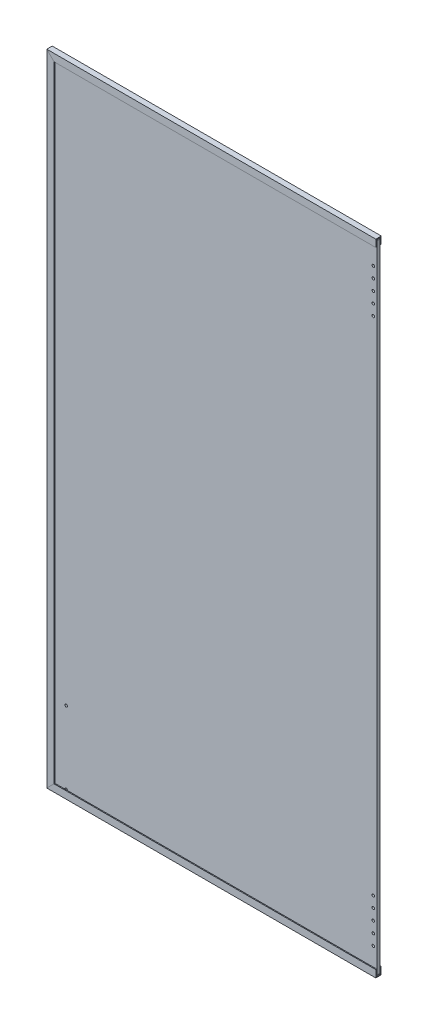
SolidWorks part; units mm, degrees
material "PC High Viscosity"
ref_plane "Front Plane" through (0, 0, 0) normal (0, 0, 1) x (1, 0, 0)
ref_plane "Top Plane" through (0, 0, 0) normal (0, 1, 0) x (1, 0, 0)
ref_plane "Right Plane" through (0, 0, 0) normal (1, 0, 0) x (0, 0, -1)
sketch "Shelf opening" plane through (0, 0, 0) normal (0, 0, 1) x (1, 0, 0)
  line L1 (0, 0) -> (577.85, 0)
  line L2 (0, 0) -> (0, 1092.2)
  line L3 (0, 1092.2) -> (577.85, 1092.2)
  line L4 (577.85, 0) -> (577.85, 1092.2)
  dimension "D1" = 577.85
  dimension "D2" = 1092.2
sketch "Sketch2" plane through (0, 0, 0) normal (0, 0, 1) x (1, 0, 0)
  line L0 (577.85, 0) -> (577.85, 1092.2) construction
  line L1 (3.175, 1104.9) -> (577.85, 1104.9)
  line L2 (3.175, 1104.9) -> (3.175, -12.7)
  line L3 (3.175, -12.7) -> (577.85, -12.7)
  line L4 (577.85, 1104.9) -> (577.85, -12.7)
  line L5 (0, 1092.2) -> (577.85, 1092.2) construction
  line L6 (0, 0) -> (0, 1092.2) construction
  line L7 (0, 0) -> (577.85, 0) construction
  dimension "D1" = 12.7
  dimension "D2" = 3.175
  dimension "D3" = 12.7
extrude "Frame outer dimensions" add sketch "Sketch2" along normal mid plane 9.525
sketch "Sketch3" plane through (0, 0, 4.7625) normal (0, 0, 1) x (1, 0, 0)
  line L0 (577.85, -12.7) -> (577.85, 1104.9) construction
  line L1 (577.85, 1092.2) -> (15.875, 1092.2)
  line L2 (577.85, 1092.2) -> (577.85, 0)
  line L3 (577.85, 0) -> (15.875, 0)
  line L4 (15.875, 1092.2) -> (15.875, 0)
  line L5 (577.85, 1104.9) -> (3.175, 1104.9) construction
  line L6 (3.175, 1104.9) -> (3.175, -12.7) construction
  line L7 (3.175, -12.7) -> (577.85, -12.7) construction
  dimension "D1" = 12.7
  dimension "D2" = 12.7
  dimension "D3" = 12.7
extrude "Frame inner dimensions" cut sketch "Sketch3" against normal through all
sketch "Sketch4" plane through (0, 0, 0) normal (0, 0, 1) x (1, 0, 0)
  line L0 (577.85, 1092.2) -> (577.85, 1104.9) construction
  line L1 (577.85, 1103.3125) -> (4.7625, 1103.3125)
  line L2 (577.85, 1103.3125) -> (577.85, -11.1125)
  line L3 (577.85, -11.1125) -> (4.7625, -11.1125)
  line L4 (4.7625, 1103.3125) -> (4.7625, -11.1125)
  line L5 (577.85, 1104.9) -> (3.175, 1104.9) construction
  line L6 (3.175, 1104.9) -> (3.175, -12.7) construction
  line L7 (3.175, -12.7) -> (577.85, -12.7) construction
  dimension "D1" = 1.5875
  dimension "D2" = 1.5875
  dimension "D3" = 1.5875
extrude "Frame profile" cut sketch "Sketch4" along normal offset from surface 1.5875 and the other way offset from surface 1.5875 up to face at (293.6875, 546.1, 4.7625) other way up to face at (293.6875, 546.1, -4.7625)
sketch "Frame sections" plane through (0, 0, 4.7625) normal (0, 0, 1) x (1, 0, 0)
  line L0 (3.175, 1104.9) -> (15.875, 1092.2)
  line L1 (3.175, -12.7) -> (15.875, 0)
split "Frame section split" trim tools "Frame sections" bodies to split 103 resulting bodies 105 106 107
sketch "Sketch5" plane through (0, 0, 0) normal (0, 0, 1) x (1, 0, 0)
  line L0 (577.85, 1092.2) -> (577.85, 1104.9) construction
  line L1 (577.85, 1101.725) -> (6.35, 1101.725)
  line L2 (577.85, 1101.725) -> (577.85, -9.525)
  line L3 (577.85, -9.525) -> (6.35, -9.525)
  line L4 (6.35, 1101.725) -> (6.35, -9.525)
  line L5 (4.7625, 1103.3125) -> (577.85, 1103.3125) construction
  line L6 (4.7625, -11.1125) -> (4.7625, 1103.3125) construction
  line L7 (577.85, -11.1125) -> (4.7625, -11.1125) construction
  dimension "D1" = 1.5875
  dimension "D2" = 1.5875
  dimension "D3" = 1.5875
  dimension "D4" = 571.5
  dimension "D5" = 1111.25
extrude "Door panel" add sketch "Sketch5" along normal mid plane 5.588 separate body
sketch "Hinge positions" plane through (0, 0, 2.794) normal (0, 0, 1) x (1, 0, 0)
  line L0 (577.85, -9.525) -> (577.85, 1101.725) construction
  line L1 (577.85, 1069.975) -> (565.15, 1069.975)
  line L2 (577.85, 1069.975) -> (577.85, 974.725)
  line L3 (577.85, 974.725) -> (565.15, 974.725)
  line L4 (565.15, 1069.975) -> (565.15, 974.725)
  line L5 (565.15, 117.475) -> (577.85, 117.475)
  line L6 (565.15, 117.475) -> (565.15, 22.225)
  line L7 (565.15, 22.225) -> (577.85, 22.225)
  line L8 (577.85, 117.475) -> (577.85, 22.225)
  line L10 (0, 0) -> (577.85, 0) construction
  line L11 (0, 1092.2) -> (577.85, 1092.2) construction
  dimension "D1" = 95.25
  dimension "D2" = 12.7
  dimension "D3" = 22.225
  dimension "D4" = 22.225
  dimension "D5" = 952.5
sketch "Sketch8" plane through (0, 0, 2.794) normal (0, 0, 1) x (1, 0, 0)
  line L0 (565.15, 69.85) -> (577.85, 69.85) construction
  line L2 (565.15, 117.475) -> (565.15, 22.225) construction
  line L3 (577.85, 117.475) -> (577.85, 22.225) construction
  line L4 (565.15, 1022.35) -> (577.85, 1022.35) construction
  line L6 (565.15, 1069.975) -> (565.15, 974.725) construction
  line L7 (577.85, 1069.975) -> (577.85, 974.725) construction
  point P0 (571.5, 31.75)
  point P11 (571.5, 50.8)
  point P12 (571.5, 69.85)
  point P13 (571.5, 88.9)
  point P14 (571.5, 107.95)
  point P15 (571.5, 1003.3)
  point P16 (571.5, 1022.35)
  point P17 (571.5, 1041.4)
  point P18 (571.5, 1060.45)
  point P19 (571.5, 984.25)
  dimension "D3" = 19.05
  dimension "D1" = 5
  dimension "D2" = 2
hole_wizard "#8 Clearance Hole1" positions "Sketch8" profile "Sketch9" hole size "#8" standard "ANSI Inch" end condition through all
sketch "Sketch9" plane through (571.5, 31.75, 2.794) normal (1, 0, 0) x (0, -1, 0)
  line L0 (0, 0) -> (0, 7.5565)
  line L1 (0, 7.5565) -> (2.2479, 7.5565)
  line L2 (2.2479, 7.5565) -> (2.2479, 0)
  line L5 (2.2479, 0) -> (0, 0)
  line L11 (0, -6.35) -> (0, 107.95) construction
  dimension "Thru Hole Dia." = 4.4958
  dimension "Thru Hole Depth" = 7.5565
sketch "Handle position" plane through (0, 0, 2.794) normal (0, 0, 1) x (1, 0, 0)
  line L0 (6.35, 1101.725) -> (6.35, -9.525) construction
  line L1 (6.35, 139.7) -> (44.45, 139.7)
  line L2 (6.35, 139.7) -> (6.35, -9.525)
  line L3 (6.35, -9.525) -> (44.45, -9.525)
  line L4 (44.45, 139.7) -> (44.45, -9.525)
  line L5 (6.35, -9.525) -> (577.85, -9.525) construction
  dimension "D1" = 149.225
  dimension "D2" = 38.1
sketch "Sketch11" plane through (0, 0, 2.794) normal (0, 0, 1) x (1, 0, 0)
  line L0 (34.925, 127) -> (34.925, 0) construction
  line L2 (6.35, 139.7) -> (6.35, -9.525) construction
  line L3 (6.35, -9.525) -> (44.45, -9.525) construction
  point P0 (34.925, 0)
  point P2 (34.925, 127)
  dimension "D1" = 28.575
  dimension "D2" = 9.525
  dimension "D3" = 136.525
hole_wizard "#8 Clearance Hole2" positions "Sketch11" profile "Sketch12" hole size "#8" standard "ANSI Inch" end condition through all
sketch "Sketch12" plane through (34.925, 0, 2.794) normal (1, 0, 0) x (0, -1, 0)
  line L0 (0, 0) -> (0, 7.5565)
  line L1 (0, 7.5565) -> (2.2479, 7.5565)
  line L2 (2.2479, 7.5565) -> (2.2479, 0)
  line L5 (2.2479, 0) -> (0, 0)
  line L11 (0, -6.35) -> (0, 107.95) construction
  dimension "Thru Hole Dia." = 4.4958
  dimension "Thru Hole Depth" = 7.5565
mirror "Mirror1" about plane through (0, 0, 0) normal (1, 0, 0) of bodies 105 106 107 113 108
delete or keep bodies "Body-Delete/Keep 1" type keep bodies bodies 105 106 107 113
delete or keep bodies "Body-Delete/Keep 2" [suppressed] type keep bodies bodies 109 110 111 112
